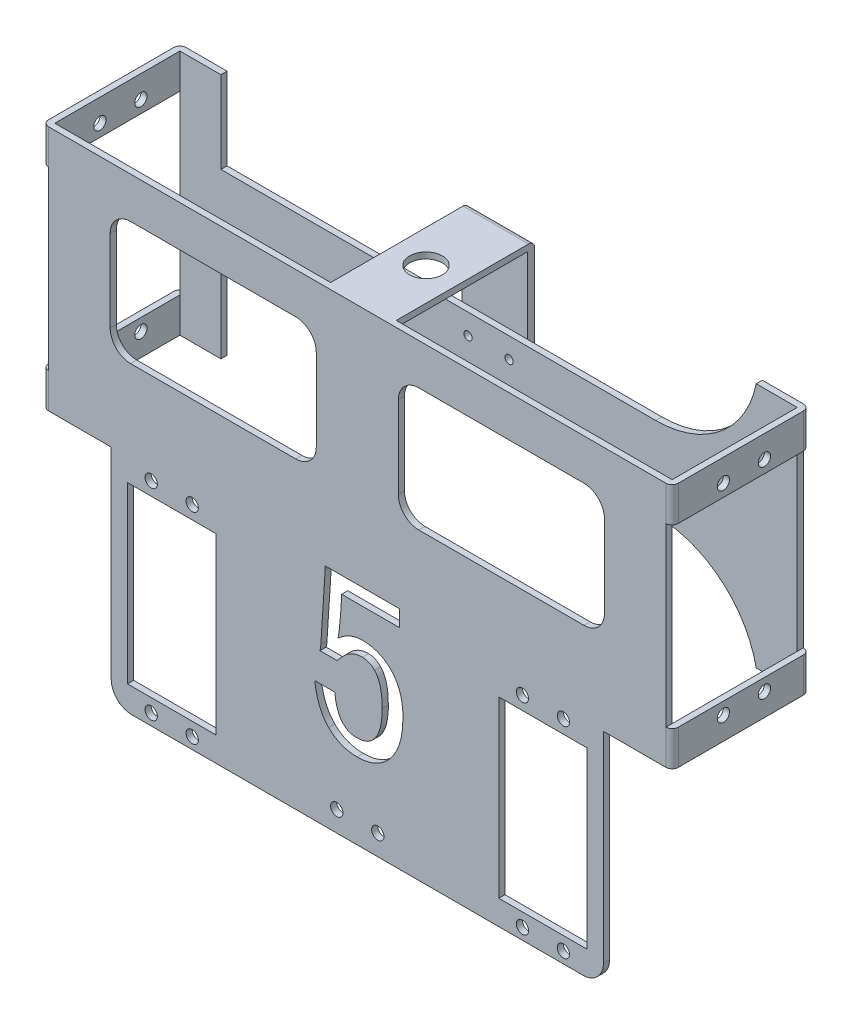
SolidWorks part; units mm, degrees
ref_plane "Front Plane" through (0, 0, 0) normal (0, 0, 1) x (1, 0, 0)
ref_plane "Top Plane" through (0, 0, 0) normal (0, 1, 0) x (1, 0, 0)
ref_plane "Right Plane" through (0, 0, 0) normal (1, 0, 0) x (0, 0, -1)
sketch "Sketch1" plane through (0, 0, 0) normal (0, 0, 1) x (1, 0, 0)
  line L0 (0, 0) -> (120, 0)
  line L1 (120, 0) -> (120, 54)
  line L2 (0, 0) -> (0, 54)
  line L3 (120, 54) -> (135.25, 54)
  line L4 (135.25, 54) -> (135.25, 114)
  line L5 (135.25, 114) -> (-15.25, 114)
  line L6 (-15.25, 114) -> (-15.25, 54)
  line L7 (-15.25, 54) -> (0, 54)
  line L8 (105.25, 6) -> (105.25, 48.5) construction
  line L9 (4, 48.5) -> (25.5, 48.5)
  line L10 (4, 48.5) -> (4, 6)
  line L11 (4, 6) -> (25.5, 6)
  line L12 (25.5, 48.5) -> (25.5, 6)
  line L13 (94.5, 48.5) -> (116, 48.5)
  line L14 (94.5, 48.5) -> (94.5, 6)
  line L15 (94.5, 6) -> (116, 6)
  line L16 (116, 48.5) -> (116, 6)
  line L17 (105.75, 104) -> (135.25, 104) construction
  line L19 (105.75, 64) -> (135.25, 64) construction
  line L20 (135.25, 104) -> (135.25, 64) construction
  line L21 (-15.25, 104) -> (14.25, 104) construction
  line L22 (-15.25, 104) -> (-15.25, 64) construction
  line L23 (-15.25, 64) -> (14.25, 64) construction
  line L24 (14.25, 104) -> (14.25, 64) construction
  line L31 (60, 0) -> (60, 114) construction
  line L62 (94.5, 27.25) -> (116, 27.25) construction
  line L66 (-0.25, 104) -> (50, 104)
  line L67 (50, 104) -> (50, 74)
  line L68 (50, 74) -> (-0.25, 74)
  line L69 (-0.25, 74) -> (-0.25, 104)
  line L70 (70, 104) -> (70, 74)
  line L71 (70, 74) -> (120.25, 74)
  line L72 (120.25, 74) -> (120.25, 104)
  line L73 (120.25, 104) -> (70, 104)
  circle A12 centre (100.25, 51.75) radius 1.5
  circle A13 centre (110.25, 51.75) radius 1.5
  circle A14 centre (110.25, 2.75) radius 1.5
  circle A15 centre (100.25, 2.75) radius 1.5
  circle A16 centre (9.75, 2.75) radius 1.5
  circle A17 centre (19.75, 2.75) radius 1.5
  circle A18 centre (9.75, 51.75) radius 1.5
  circle A19 centre (19.75, 51.75) radius 1.5
  circle A24 centre (55, 5) radius 1.5
  circle A25 centre (65, 5) radius 1.5
  dimension "D30" = 3
  dimension "D32" = 5
  dimension "D44" = 3
  dimension "D45" = 10
  dimension "D46" = 5
  dimension "D14" = 46
  dimension "D1" = 120
  dimension "D2" = 54
  dimension "D3" = 60
  dimension "D4" = 4
  dimension "D5" = 4
  dimension "D6" = 6
  dimension "D7" = 6
  dimension "D8" = 21.5
  dimension "D9" = 21.5
  dimension "D10" = 42.5
  dimension "D11" = 10
  dimension "D12" = 10
  dimension "D13" = 30
  dimension "D15" = 29.5
  dimension "D40" = 15
  dimension "D41" = 10
  dimension "D42" = 10
  dimension "D43" = 10
extrude "Boss-Extrude1" add sketch "Sketch1" along normal blind 1.5 contours L6 L7 L2 L0 L1 L3 L4 L5 A19 A18 A17 A15 A14 L68 L69 L66 L67 L9 L12 L11 L10 L13 L16 L15 L14 L73 L72 L71 L70 A12 A13 A16 | L4 | L4 | L6 | L6 | L5 region at (60, 57.9168, 0)
fillet "Fillet2" radius 5 10 edges at (-0.25, 104, 0.75) (70, 104, 0.75) (120.25, 104, 0.75) (50, 104, 0.75) (50, 74, 0.75) (120.25, 74, 0.75) (70, 74, 0.75) (-0.25, 74, 0.75) (120, 0, 0.75) (0, 0, 0.75)
sketch "Sketch3" plane through (0, 0, 1.5) normal (0, 0, 1) x (1, 0, 0)
  text T0 "5" font "MS UI Gothic" height in points 120
extrude "Cut-Extrude1" cut sketch "Sketch3" against normal blind 1.5
sketch "Sketch7" plane through (0, 0, 0) normal (0, 0, -1) x (-1, 0, 0)
  line L0 (-135.25, 54) -> (-135.25, 114) construction
  line L1 (-135.25, 114) -> (-136.75, 114)
  line L2 (-135.25, 114) -> (-135.25, 105.5)
  line L3 (-135.25, 105.5) -> (-136.75, 105.5)
  line L4 (-136.75, 114) -> (-136.75, 105.5)
  line L5 (-135.25, 62.5) -> (-136.75, 62.5)
  line L6 (-135.25, 62.5) -> (-135.25, 54)
  line L7 (-135.25, 54) -> (-136.75, 54)
  line L8 (-136.75, 62.5) -> (-136.75, 54)
  line L9 (-120, 54) -> (-135.25, 54) construction
  dimension "D1" = 8.5
  dimension "D2" = 8.5
  dimension "D3" = 1.5
extrude "Boss-Extrude4" add sketch "Sketch7" along normal blind 33.5 from offset 1.5 offset against normal yes
sketch "Sketch8" plane through (136.75, 0, 0) normal (1, 0, 0) x (0, 0, -1)
  line L0 (32, 105.5) -> (-1.5, 105.5) construction
  line L1 (0, 84) -> (32, 84) construction
  line L2 (0, 62.5) -> (0, 105.5) construction
  line L3 (16, 84) -> (16, 105.5) construction
  circle A0 centre (11, 108.5) radius 1.5
  circle A1 centre (21, 108.5) radius 1.5
  circle A2 centre (21, 59.5) radius 1.5
  circle A3 centre (11, 59.5) radius 1.5
  dimension "D1" = 3
  dimension "D2" = 46
  dimension "D3" = 10
  dimension "D4" = 5
extrude "Cut-Extrude4" cut sketch "Sketch8" against normal up to next
sketch "Sketch10" plane through (135.25, 0, 0) normal (-1, 0, 0) x (0, 0, 1)
  line L0 (-32, 54) -> (0, 54) construction
  line L1 (-32, 114) -> (-30.5, 114)
  line L2 (-32, 114) -> (-32, 54)
  line L3 (-32, 54) -> (-30.5, 54)
  line L4 (-30.5, 114) -> (-30.5, 54)
  dimension "D1" = 1.5
extrude "Boss-Extrude5" add sketch "Sketch10" along normal blind 10
sketch "Sketch11" plane through (125.25, 0, 0) normal (-1, 0, 0) x (0, 0, 1)
  line L0 (-32, 114) -> (-32, 54) construction
  line L1 (-32, 94) -> (-30.5, 94)
  line L2 (-32, 94) -> (-32, 74)
  line L3 (-32, 74) -> (-30.5, 74)
  line L4 (-30.5, 94) -> (-30.5, 74)
  line L5 (-30.5, 54) -> (-30.5, 114) construction
  point P11 (-30.5, 84)
  dimension "D1" = 20
extrude "Boss-Extrude6" add sketch "Sketch11" along normal blind 65.25
sketch "Sketch12" plane through (0, 0, -32) normal (0, 0, -1) x (-1, 0, 0)
  line L0 (-60, 74) -> (-125.25, 74) construction
  line L1 (-60, 94) -> (-125.25, 94) construction
  line L2 (-60, 94) -> (-60, 74) construction
  circle A0 centre (-65, 89) radius 1
  circle A1 centre (-65, 79) radius 1
  dimension "D1" = 2
  dimension "D2" = 5
  dimension "D3" = 5
  dimension "D4" = 5
extrude "Cut-Extrude5" cut sketch "Sketch12" against normal up to next
fillet "Fillet3" radius 1.5 4 edges at (136.75, 58.25, 1.5) (136.75, 58.25, -32) (136.75, 109.75, -32) (136.75, 109.75, 1.5)
fillet "Fillet4" radius 25 2 edges at (125.25, 74, -31.25) (125.25, 94, -31.25)
ref_plane "Plane1" through (60, 0, 0) normal (1, 0, 0) x (0, 0, -1)
mirror "Mirror3" about plane through (60, 0, 0) normal (1, 0, 0) of "Boss-Extrude4", "Cut-Extrude4", "Boss-Extrude5", "Boss-Extrude6", "Cut-Extrude5", "Fillet3"
sketch "Sketch13" plane through (0, 0, 0) normal (0, 0, -1) x (-1, 0, 0)
  line L0 (-135.25, 114) -> (15.25, 114) construction
  line L1 (-68, 114) -> (-52, 114)
  line L2 (-68, 114) -> (-68, 112.5)
  line L3 (-68, 112.5) -> (-52, 112.5)
  line L4 (-52, 114) -> (-52, 112.5)
  point P8 (-60, 114)
  dimension "D1" = 1.5
  dimension "D2" = 16
extrude "Boss-Extrude7" add sketch "Sketch13" along normal blind 33.75
sketch "Sketch14" plane through (0, 112.5, 0) normal (0, -1, 0) x (1, 0, 0)
  line L0 (-5.25, -32) -> (100.7551, -32) construction
  line L1 (52, -33.75) -> (68, -33.75)
  line L2 (52, -33.75) -> (52, -32)
  line L3 (52, -32) -> (68, -32)
  line L4 (68, -33.75) -> (68, -32)
  line L5 (68, -33.75) -> (68, 0) construction
  line L7 (52, -32) -> (68, -32)
  line L8 (52, -32) -> (52, -33.75)
  line L9 (52, -33.75) -> (68, -33.75)
  line L10 (68, -32) -> (68, -33.75)
  line M2 (52, 0) -> (52, -33.75)
  line M3 (52, -33.75) -> (68, -33.75)
  line M4 (68, -33.75) -> (68, 0)
extrude "Boss-Extrude9" add sketch "Sketch14" along normal up to vertex (38.5 mm away) contours L3 M2 M3 M4 region at (60, 112.5, -32.875) up to point (-5.25, 74, -32)
sketch "Sketch16" plane through (0, 0, -30.5) normal (0, 0, 1) x (1, 0, 0)
  circle A0 centre (55, 89) radius 1
  circle A1 centre (65, 89) radius 1
  circle A2 centre (65, 79) radius 1
  circle A3 centre (55, 79) radius 1
extrude "Cut-Extrude7" cut sketch "Sketch16" against normal through all
fillet "Fillet5" radius 1.5 1 edges at (60, 114, -33.75)
sketch "Sketch17" plane through (0, 114, 0) normal (0, 1, 0) x (1, 0, 0)
  line L0 (68, 32.25) -> (68, 0) construction
  line L2 (-15.25, 15.25) -> (135.25, 15.25) construction
  line L4 (-15.25, 30.5) -> (-15.25, 0) construction
  line L5 (135.25, 30.5) -> (135.25, 0) construction
  circle A0 centre (60, 15.25) radius 4
  dimension "D1" = 8
  dimension "D2" = 8
extrude "Cut-Extrude8" cut sketch "Sketch17" against normal up to next
